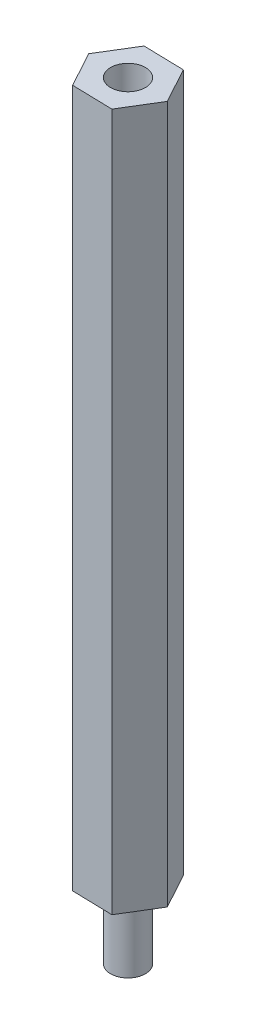
SolidWorks part; units mm, degrees
ref_plane "정면" through (0, 0, 0) normal (0, 0, 1) x (1, 0, 0)
ref_plane "윗면" through (0, 0, 0) normal (0, 1, 0) x (1, 0, 0)
ref_plane "우측면" through (0, 0, 0) normal (1, 0, 0) x (0, 0, -1)
sketch "스케치1" plane through (0, 0, 0) normal (0, 1, 0) x (1, 0, 0)
  line L1 (1.6557, -3.0428) -> (3.463, -0.0876)
  line L2 (3.463, -0.0876) -> (1.8073, 2.9553)
  line L3 (1.8073, 2.9553) -> (-1.6557, 3.0428)
  line L4 (-1.6557, 3.0428) -> (-3.463, 0.0876)
  line L5 (-3.463, 0.0876) -> (-1.8073, -2.9553)
  line L6 (-1.8073, -2.9553) -> (1.6557, -3.0428)
  circle A0 centre (0, 0) radius 3 construction
  dimension "D1" = 6
extrude "보스-돌출1" add sketch "스케치1" along normal blind 60
sketch "스케치2" plane through (0, 60, 0) normal (0, 1, 0) x (1, 0, 0)
  circle A0 centre (0, 0) radius 1.5
  dimension "D1" = 3
extrude "컷-돌출1" cut sketch "스케치2" against normal blind 8
sketch "스케치3" plane through (0, 0, 0) normal (0, -1, 0) x (1, 0, 0)
  circle A0 centre (0, 0) radius 1.5
  dimension "D1" = 3
extrude "보스-돌출2" add sketch "스케치3" along normal blind 6
